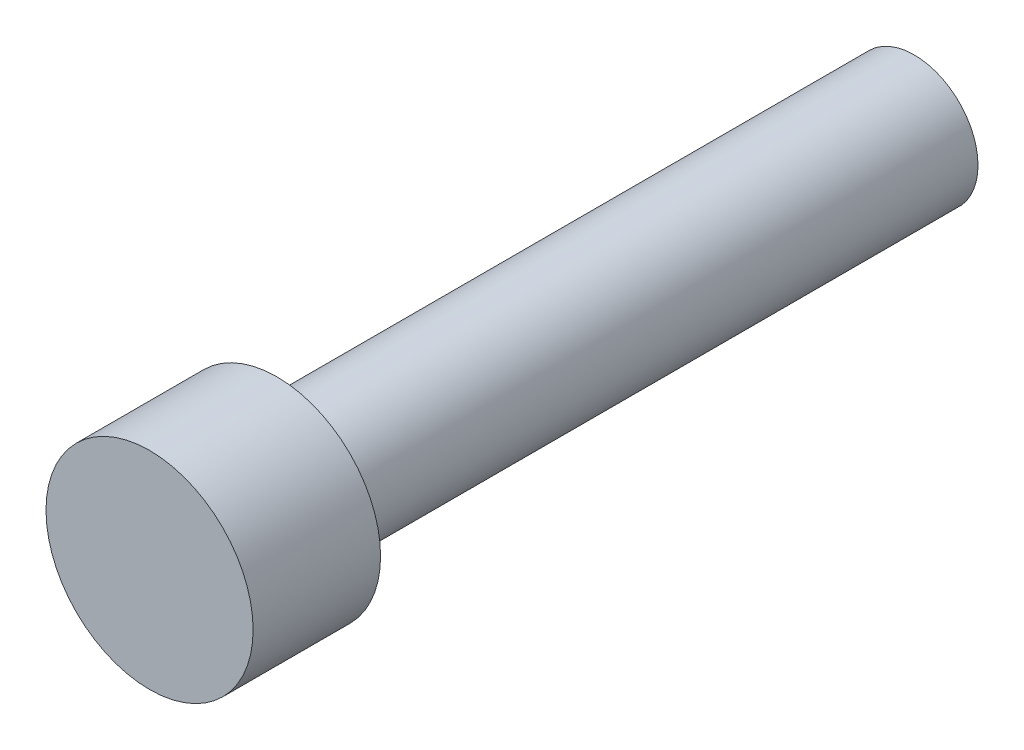
SolidWorks part; units mm, degrees
ref_plane "前视基准面" through (0, 0, 0) normal (0, 0, 1) x (1, 0, 0)
ref_plane "上视基准面" through (0, 0, 0) normal (0, 1, 0) x (1, 0, 0)
ref_plane "右视基准面" through (0, 0, 0) normal (1, 0, 0) x (0, 0, -1)
other "Configuration Table"
sketch "Sketch1" plane through (0, 0, 0) normal (0, 0, 1) x (1, 0, 0)
  circle A0 centre (0, 0) radius 6.5
extrude "Boss-Extrude1" add sketch "Sketch1" along normal blind 8
sketch "Sketch2" plane through (0, 0, 0) normal (0, 0, 1) x (1, 0, 0)
  circle A0 centre (0, 0) radius 4
extrude "Boss-Extrude2" add sketch "Sketch2" against normal blind 40
ref_plane "head_bottom_face" through (0, 0, 0) normal (0, 0, 1) x (1, 0, 0)
sketch3d "3DSketch1"
  line L0 (0, 0, 8) -> (0, 0, -40) construction
ref_axis "screw_axis" through (0, 0, 8) along (0, 0, -1)
